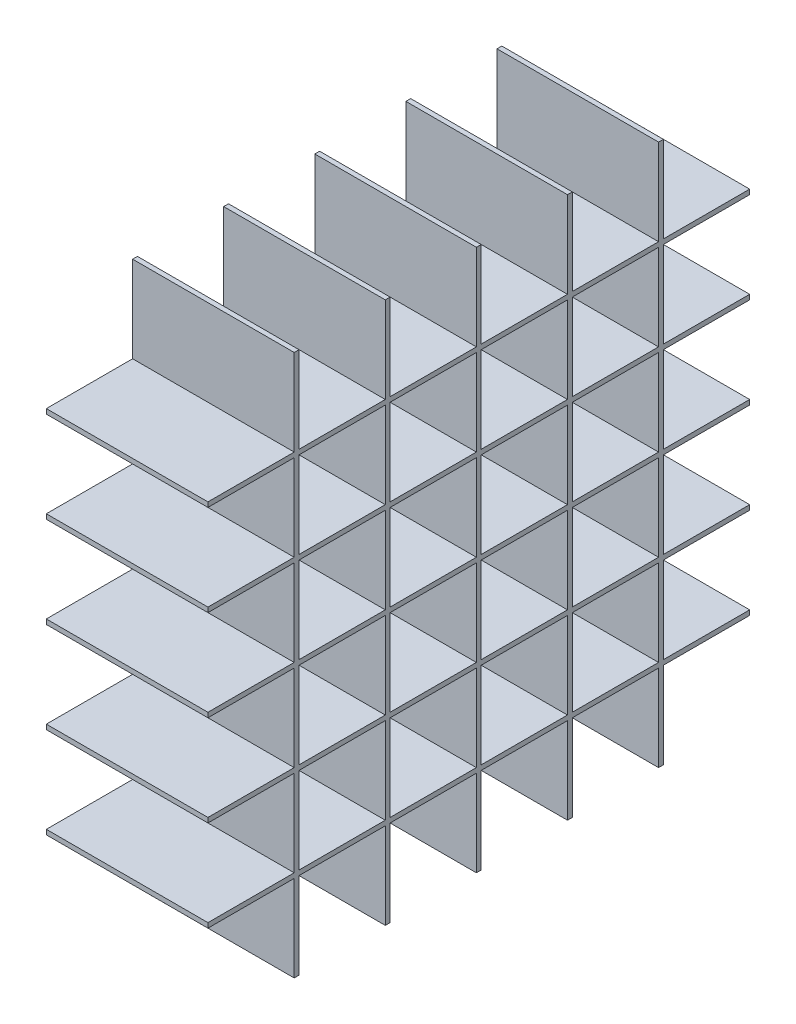
SolidWorks part; units mm, degrees
material "3003 Alloy"
ref_plane "Front Plane" through (0, 0, 0) normal (0, 0, 1) x (1, 0, 0)
ref_plane "Top Plane" through (0, 0, 0) normal (0, 1, 0) x (1, 0, 0)
ref_plane "Right Plane" through (0, 0, 0) normal (1, 0, 0) x (0, 0, -1)
sketch "Sketch1" plane through (0, 0, 0) normal (1, 0, 0) x (0, 0, -1)
  line L1 (-114.3, 114.3) -> (114.3, 114.3)
  line L2 (-114.3, 114.3) -> (-114.3, -114.3)
  line L3 (-114.3, -114.3) -> (114.3, -114.3)
  line L4 (114.3, 114.3) -> (114.3, -114.3)
  line L5 (-114.3, 114.3) -> (114.3, -114.3) construction
  line L6 (-114.3, -114.3) -> (114.3, 114.3) construction
  point P0 (0, 0)
  dimension "D1" = 228.6
  dimension "D2" = 228.6
extrude "Boss-Extrude1" add sketch "Sketch1" along normal blind 67
sketch "Sketch2" plane through (67, 0, 0) normal (1, 0, 0) x (0, 0, -1)
  line L0 (-114.3, 114.3) -> (-114.3, -114.3) construction
  line L1 (-112.3, 112.3) -> (-76.534, 112.3)
  line L2 (-112.3, 112.3) -> (-112.3, 76.534)
  line L3 (-112.3, 76.534) -> (-76.534, 76.534)
  line L4 (-76.534, 112.3) -> (-76.534, 76.534)
  line L5 (114.3, 114.3) -> (-114.3, 114.3) construction
  line L6 (-75.534, 112.3) -> (-75.534, 73.2554) construction
  line L7 (-74.534, 112.3) -> (-74.534, 76.534)
  line L8 (-38.768, 76.534) -> (-74.534, 76.534)
  line L9 (-38.768, 112.3) -> (-38.768, 76.534)
  line L10 (-38.768, 112.3) -> (-74.534, 112.3)
  line L11 (-37.768, 112.3) -> (-37.768, 75.534) construction
  line L12 (36.764, 76.534) -> (0.998, 76.534)
  line L13 (36.764, 112.3) -> (36.764, 76.534)
  line L14 (36.764, 112.3) -> (0.998, 112.3)
  line L15 (0.998, 112.3) -> (0.998, 76.534)
  line L16 (-36.768, 76.534) -> (-1.002, 76.534)
  line L17 (-1.002, 112.3) -> (-1.002, 76.534)
  line L18 (-36.768, 112.3) -> (-1.002, 112.3)
  line L19 (-36.768, 112.3) -> (-36.768, 76.534)
  line L20 (37.764, 112.3) -> (37.764, 70.4589) construction
  line L21 (38.764, 76.534) -> (74.53, 76.534)
  line L22 (112.296, 76.534) -> (76.53, 76.534)
  line L23 (112.296, 112.3) -> (112.296, 76.534)
  line L24 (74.53, 112.3) -> (74.53, 76.534)
  line L25 (76.53, 112.3) -> (76.53, 76.534)
  line L26 (112.296, 112.3) -> (76.53, 112.3)
  line L27 (38.764, 112.3) -> (74.53, 112.3)
  line L28 (38.764, 112.3) -> (38.764, 76.534)
  line L29 (-112.3, 75.534) -> (114.3, 75.534) construction
  line L30 (114.3, -114.3) -> (114.3, 114.3) construction
  line L31 (38.764, 74.534) -> (74.53, 74.534)
  line L32 (112.296, 74.534) -> (76.53, 74.534)
  line L33 (112.296, 38.768) -> (76.53, 38.768)
  line L34 (38.764, 38.768) -> (74.53, 38.768)
  line L35 (36.764, 74.534) -> (0.998, 74.534)
  line L36 (36.764, 38.768) -> (0.998, 38.768)
  line L37 (36.764, 38.768) -> (36.764, 74.534)
  line L38 (38.764, 38.768) -> (38.764, 74.534)
  line L39 (74.53, 38.768) -> (74.53, 74.534)
  line L40 (76.53, 38.768) -> (76.53, 74.534)
  line L41 (112.296, 38.768) -> (112.296, 74.534)
  line L42 (0.998, 38.768) -> (0.998, 74.534)
  line L43 (-1.002, 38.768) -> (-1.002, 74.534)
  line L44 (-36.768, 74.534) -> (-1.002, 74.534)
  line L45 (-36.768, 38.768) -> (-36.768, 74.534)
  line L46 (-36.768, 38.768) -> (-1.002, 38.768)
  line L47 (-38.768, 74.534) -> (-74.534, 74.534)
  line L48 (-38.768, 38.768) -> (-38.768, 74.534)
  line L49 (-38.768, 38.768) -> (-74.534, 38.768)
  line L50 (-74.534, 38.768) -> (-74.534, 74.534)
  line L51 (-76.534, 38.768) -> (-76.534, 74.534)
  line L52 (-112.3, 74.534) -> (-76.534, 74.534)
  line L53 (-112.3, 38.768) -> (-112.3, 74.534)
  line L54 (-112.3, 38.768) -> (-76.534, 38.768)
  line L55 (-112.3, 37.768) -> (112.296, 37.768) construction
  line L56 (-112.3, 36.768) -> (-112.3, 1.002)
  line L57 (-112.3, 1.002) -> (-76.534, 1.002)
  line L58 (-112.3, 36.768) -> (-76.534, 36.768)
  line L59 (-38.768, 36.768) -> (-74.534, 36.768)
  line L60 (-38.768, 1.002) -> (-74.534, 1.002)
  line L61 (-76.534, 36.768) -> (-76.534, 1.002)
  line L62 (-74.534, 36.768) -> (-74.534, 1.002)
  line L63 (-36.768, 1.002) -> (-1.002, 1.002)
  line L64 (-38.768, 36.768) -> (-38.768, 1.002)
  line L65 (-36.768, 36.768) -> (-36.768, 1.002)
  line L66 (-36.768, 36.768) -> (-1.002, 36.768)
  line L67 (-1.002, 36.768) -> (-1.002, 1.002)
  line L68 (0.998, 36.768) -> (0.998, 1.002)
  line L69 (36.764, 36.768) -> (0.998, 36.768)
  line L70 (36.764, 36.768) -> (36.764, 1.002)
  line L71 (36.764, 1.002) -> (0.998, 1.002)
  line L72 (38.764, 1.002) -> (74.53, 1.002)
  line L73 (38.764, 36.768) -> (38.764, 1.002)
  line L74 (38.764, 36.768) -> (74.53, 36.768)
  line L75 (74.53, 36.768) -> (74.53, 1.002)
  line L76 (76.53, 36.768) -> (76.53, 1.002)
  line L77 (112.296, 36.768) -> (76.53, 36.768)
  line L78 (112.296, 36.768) -> (112.296, 1.002)
  line L79 (112.296, 1.002) -> (76.53, 1.002)
  line L80 (112.296, -0.998) -> (76.53, -0.998)
  line L81 (112.296, -36.764) -> (112.296, -0.998)
  line L82 (112.296, -36.764) -> (76.53, -36.764)
  line L83 (76.53, -36.764) -> (76.53, -0.998)
  line L84 (74.53, -36.764) -> (74.53, -0.998)
  line L85 (38.764, -0.998) -> (74.53, -0.998)
  line L86 (38.764, -36.764) -> (38.764, -0.998)
  line L87 (38.764, -36.764) -> (74.53, -36.764)
  line L88 (36.764, -0.998) -> (0.998, -0.998)
  line L89 (36.764, -36.764) -> (36.764, -0.998)
  line L90 (36.764, -36.764) -> (0.998, -36.764)
  line L91 (0.998, -36.764) -> (0.998, -0.998)
  line L92 (-1.002, -36.764) -> (-1.002, -0.998)
  line L93 (-36.768, -0.998) -> (-1.002, -0.998)
  line L94 (-36.768, -36.764) -> (-36.768, -0.998)
  line L95 (-36.768, -36.764) -> (-1.002, -36.764)
  line L96 (-38.768, -36.764) -> (-38.768, -0.998)
  line L97 (-38.768, -0.998) -> (-74.534, -0.998)
  line L98 (-74.534, -36.764) -> (-74.534, -0.998)
  line L99 (-38.768, -36.764) -> (-74.534, -36.764)
  line L100 (-76.534, -36.764) -> (-76.534, -0.998)
  line L101 (-112.3, -0.998) -> (-76.534, -0.998)
  line L102 (-112.3, -36.764) -> (-112.3, -0.998)
  line L103 (-112.3, -36.764) -> (-76.534, -36.764)
  line L104 (-112.3, -37.764) -> (112.296, -37.764) construction
  line L105 (38.764, -38.764) -> (74.53, -38.764)
  line L106 (112.296, -38.764) -> (76.53, -38.764)
  line L107 (112.296, -38.764) -> (112.296, -74.53)
  line L108 (112.296, -112.296) -> (112.296, -76.53)
  line L109 (112.296, -112.296) -> (76.53, -112.296)
  line L110 (76.53, -112.296) -> (76.53, -76.53)
  line L111 (112.296, -76.53) -> (76.53, -76.53)
  line L112 (112.296, -74.53) -> (76.53, -74.53)
  line L113 (76.53, -38.764) -> (76.53, -74.53)
  line L114 (74.53, -38.764) -> (74.53, -74.53)
  line L115 (74.53, -112.296) -> (74.53, -76.53)
  line L116 (38.764, -112.296) -> (74.53, -112.296)
  line L117 (38.764, -76.53) -> (74.53, -76.53)
  line L118 (38.764, -74.53) -> (74.53, -74.53)
  line L119 (38.764, -38.764) -> (38.764, -74.53)
  line L120 (38.764, -112.296) -> (38.764, -76.53)
  line L121 (36.764, -112.296) -> (36.764, -76.53)
  line L122 (36.764, -112.296) -> (0.998, -112.296)
  line L123 (36.764, -76.53) -> (0.998, -76.53)
  line L124 (36.764, -74.53) -> (0.998, -74.53)
  line L125 (36.764, -38.764) -> (36.764, -74.53)
  line L126 (36.764, -38.764) -> (0.998, -38.764)
  line L127 (-1.002, -38.764) -> (-1.002, -74.53)
  line L128 (0.998, -38.764) -> (0.998, -74.53)
  line L129 (0.998, -112.296) -> (0.998, -76.53)
  line L130 (-1.002, -112.296) -> (-1.002, -76.53)
  line L131 (-36.768, -76.53) -> (-1.002, -76.53)
  line L132 (-36.768, -74.53) -> (-1.002, -74.53)
  line L133 (-36.768, -38.764) -> (-1.002, -38.764)
  line L134 (-36.768, -112.296) -> (-1.002, -112.296)
  line L135 (-38.768, -112.296) -> (-38.768, -76.53)
  line L136 (-36.768, -112.296) -> (-36.768, -76.53)
  line L137 (-36.768, -38.764) -> (-36.768, -74.53)
  line L138 (-38.768, -38.764) -> (-38.768, -74.53)
  line L139 (-38.768, -38.764) -> (-74.534, -38.764)
  line L140 (-74.534, -38.764) -> (-74.534, -74.53)
  line L141 (-38.768, -74.53) -> (-74.534, -74.53)
  line L142 (-38.768, -76.53) -> (-74.534, -76.53)
  line L143 (-74.534, -112.296) -> (-74.534, -76.53)
  line L144 (-38.768, -112.296) -> (-74.534, -112.296)
  line L145 (-112.3, -112.296) -> (-76.534, -112.296)
  line L146 (-112.3, -74.53) -> (-76.534, -74.53)
  line L147 (-112.3, -38.764) -> (-112.3, -74.53)
  line L148 (-112.3, -38.764) -> (-76.534, -38.764)
  line L149 (-112.3, -112.296) -> (-112.3, -76.53)
  line L150 (-112.3, -76.53) -> (-76.534, -76.53)
  line L151 (-76.534, -112.296) -> (-76.534, -76.53)
  line L152 (-76.534, -38.764) -> (-76.534, -74.53)
  point P114 (-56.651, -36.764)
  dimension "D1" = 2
  dimension "D2" = 2
  dimension "D3" = 35.766
  dimension "D4" = 35.766
  dimension "D5" = 1
  dimension "D6" = 1
  dimension "D7" = 1
  dimension "D8" = 1
  dimension "D9" = 1
  dimension "D10" = 1
extrude "Cut-Extrude1" cut sketch "Sketch2" against normal blind 76.2
sketch "Sketch4" plane through (0, -114.3, 0) normal (0, 1, 0) x (1, 0, 0)
  line L0 (67, -112.3) -> (0, -112.3)
  line L1 (67, -76.534) -> (0, -76.534)
  line L2 (67, -74.534) -> (0, -74.534)
  line L3 (67, -38.768) -> (0, -38.768)
  line L4 (67, -36.768) -> (0, -36.768)
  line L5 (67, -1.002) -> (0, -1.002)
  line L6 (67, 0.998) -> (0, 0.998)
  line L7 (67, 36.764) -> (0, 36.764)
  line L8 (67, 38.764) -> (0, 38.764)
  line L9 (67, 74.53) -> (0, 74.53)
  line L10 (67, 76.53) -> (0, 76.53)
  line L11 (67, 112.296) -> (0, 112.296)
  line L12 (0, 112.296) -> (0, 76.53)
  line L13 (67, 112.296) -> (67, 76.53)
  line L14 (0, 74.53) -> (0, 38.764)
  line L15 (67, 74.53) -> (67, 38.764)
  line L16 (0, 36.764) -> (0, 0.998)
  line L17 (67, 36.764) -> (67, 0.998)
  line L18 (67, -1.002) -> (67, -36.768)
  line L19 (0, -1.002) -> (0, -36.768)
  line L21 (0, -38.768) -> (0, -74.534)
  line L22 (67, -38.768) -> (67, -74.534)
  line L23 (67, -76.534) -> (67, -112.3)
  line L24 (0, -76.534) -> (0, -112.3)
extrude "Cut-Extrude3" cut sketch "Sketch4" against normal blind 4 and the other way blind 4
sketch "Sketch5" plane through (0, 0, 114.3) normal (0, 0, 1) x (1, 0, 0)
  line L0 (0, -76.53) -> (67, -76.53)
  line L1 (0, -74.53) -> (67, -74.53)
  line L2 (0, -38.764) -> (67, -38.764)
  line L3 (0, -36.764) -> (67, -36.764)
  line L4 (0, -0.998) -> (67, -0.998)
  line L5 (0, 1.002) -> (67, 1.002)
  line L6 (0, 36.768) -> (67, 36.768)
  line L7 (0, 38.768) -> (67, 38.768)
  line L8 (0, 74.534) -> (67, 74.534)
  line L9 (0, 76.534) -> (67, 76.534)
  line L10 (0, 112.3) -> (67, 112.3)
  line L11 (0, -114.3) -> (0, -76.53)
  line L12 (67, -114.3) -> (67, -76.53)
  line L13 (0, -74.53) -> (0, -38.764)
  line L14 (67, -74.53) -> (67, -38.764)
  line L15 (0, -36.764) -> (0, -0.998)
  line L16 (67, -36.764) -> (67, -0.998)
  line L17 (67, 1.002) -> (67, 36.768)
  line L18 (0, 1.002) -> (0, 36.768)
  line L19 (0, 38.768) -> (0, 74.534)
  line L20 (67, 38.768) -> (67, 74.534)
  line L21 (67, 76.534) -> (67, 112.3)
  line L22 (0, 76.534) -> (0, 112.3)
  line M1 (0, 114.3) -> (0, -114.3)
  line M2 (0, -114.3) -> (67, -114.3)
  line M3 (67, -114.3) -> (67, 114.3)
extrude "Cut-Extrude4" cut sketch "Sketch5" against normal blind 4 and the other way blind 4 contours L0 M1 M2 M3 | L2 L1 M1 M3 | L4 L3 M1 M3 | L6 L5 M1 M3 | L8 L7 M1 M3 | L10 L9 M1 M3 region at (33.5, -95.415, 114.3) region at (33.5, -56.647, 114.3) region at (33.5, -18.881, 114.3) region at (33.5, 18.885, 114.3) region at (33.5, 56.651, 114.3) region at (33.5, 94.417, 114.3)
sketch "Sketch6" plane through (0, 0, -114.3) normal (0, 0, 1) x (1, 0, 0)
  line L0 (0, 112.3) -> (67, 112.3)
  line L1 (0, 76.534) -> (67, 76.534)
  line L2 (0, 74.534) -> (67, 74.534)
  line L3 (0, 38.768) -> (67, 38.768)
  line L4 (0, 36.768) -> (67, 36.768)
  line L5 (0, -0.998) -> (67, -0.998)
  line L6 (0, 1.002) -> (67, 1.002)
  line L7 (0, -76.53) -> (67, -76.53)
  line L8 (0, -74.53) -> (67, -74.53)
  line L9 (0, -36.764) -> (67, -36.764)
  line L10 (0, -38.764) -> (67, -38.764)
  line L11 (0, 112.3) -> (0, 76.534)
  line L12 (0, 74.534) -> (0, 38.768)
  line L13 (0, 36.768) -> (0, 1.002)
  line L14 (0, -0.998) -> (0, -36.764)
  line L15 (0, -38.764) -> (0, -74.53)
  line L16 (0, -76.53) -> (0, -114.3)
  line L17 (67, 112.3) -> (67, 76.534)
  line L18 (67, 74.534) -> (67, 38.768)
  line L19 (67, 36.768) -> (67, 1.002)
  line L20 (67, -0.998) -> (67, -36.764)
  line L21 (67, -38.764) -> (67, -74.53)
  line L22 (67, -76.53) -> (67, -114.3)
  line M1 (0, -114.3) -> (0, 114.3)
  line M3 (67, 114.3) -> (67, -114.3)
  line M4 (67, -114.3) -> (0, -114.3)
extrude "Cut-Extrude5" cut sketch "Sketch6" against normal blind 4 and the other way blind 4 contours L1 L0 M1 M3 | L3 L2 M1 M3 | L6 L4 M1 M3 | L9 L5 M1 M3 | L10 L8 M1 M3 | L7 M1 M3 M4 region at (33.5, 94.417, -114.3) region at (33.5, 56.651, -114.3) region at (33.5, 18.885, -114.3) region at (33.5, -18.881, -114.3) region at (33.5, -56.647, -114.3) region at (33.5, -95.415, -114.3)
sketch "Sketch9" plane through (0, 114.3, 0) normal (0, 1, 0) x (1, 0, 0)
  line L0 (0, -76.534) -> (67, -76.534)
  line L1 (0, -74.534) -> (67, -74.534)
  line L2 (0, -38.768) -> (67, -38.768)
  line L3 (0, -36.768) -> (67, -36.768)
  line L4 (0, -1.002) -> (67, -1.002)
  line L5 (0, 0.998) -> (67, 0.998)
  line L6 (0, 36.764) -> (67, 36.764)
  line L7 (0, 38.764) -> (67, 38.764)
  line L8 (0, 74.53) -> (67, 74.53)
  line L9 (0, 76.53) -> (67, 76.53)
  line L10 (0, -114.3) -> (0, -76.534)
  line L11 (0, -74.534) -> (0, -38.768)
  line L12 (0, -36.768) -> (0, -1.002)
  line L13 (0, 0.998) -> (0, 36.764)
  line L14 (0, 38.764) -> (0, 74.53)
  line L15 (0, 76.53) -> (0, 114.3)
  line L16 (67, -114.3) -> (67, -76.534)
  line L17 (67, -74.534) -> (67, -38.768)
  line L18 (67, -36.768) -> (67, -1.002)
  line L19 (67, 0.998) -> (67, 36.764)
  line L20 (67, 38.764) -> (67, 74.53)
  line L21 (67, 76.53) -> (67, 114.3)
  line M1 (0, 114.3) -> (0, -114.3)
  line M2 (0, -114.3) -> (67, -114.3)
  line M3 (67, -114.3) -> (67, 114.3)
  line M4 (67, 114.3) -> (0, 114.3)
extrude "Cut-Extrude6" cut sketch "Sketch9" against normal blind 4 and the other way blind 4 contours L0 M1 M2 M3 | L2 L1 M1 M3 | L4 L3 M1 M3 | L6 L5 M1 M3 | L8 L7 M1 M3 | L9 M1 M3 M4 region at (33.5, 114.3, 95.417) region at (33.5, 114.3, 56.651) region at (33.5, 114.3, 18.885) region at (33.5, 114.3, -18.881) region at (33.5, 114.3, -56.647) region at (33.5, 114.3, -95.415)
sketch "Sketch10" plane through (0, 0, 76.534) normal (0, 0, 1) x (1, 0, 0)
  line L0 (0, -114.3) -> (67, -114.3)
  line L1 (67, -114.3) -> (67, -112.3)
  line L2 (67, -114.3) -> (67, -76.53) construction
  line L3 (67, -112.3) -> (0, -112.3)
  line L4 (0, -114.3) -> (0, -76.53) construction
  line L5 (0, -112.3) -> (0, -114.3)
  line L6 (0, 114.3) -> (67, 114.3)
  line L7 (67, 114.3) -> (67, 112.3)
  line L8 (67, 76.534) -> (67, 114.3) construction
  line L9 (67, 112.3) -> (0, 112.3)
  line L10 (0, 76.534) -> (0, 114.3) construction
  line L11 (0, 112.3) -> (0, 114.3)
  dimension "D1" = 2
  dimension "D2" = 2
extrude "Cut-Extrude7" cut sketch "Sketch10" against normal through all
sketch "Sketch11" plane through (0, -76.53, 0) normal (0, -1, 0) x (-1, 0, 0)
  line L0 (-67, 114.3) -> (0, 114.3)
  line L1 (0, 114.3) -> (0, 112.3)
  line L2 (0, 114.3) -> (0, 76.53) construction
  line L3 (0, 112.3) -> (-67, 112.3)
  line L4 (-67, 114.3) -> (-67, 76.53) construction
  line L5 (-67, 112.3) -> (-67, 114.3)
  line L6 (-67, 114.3) -> (-76.1621, 114.1122)
  line L7 (-67, -114.3) -> (0, -114.3)
  line L8 (0, -114.3) -> (0, -112.3)
  line L9 (0, -76.534) -> (0, -114.3) construction
  line L10 (0, -112.3) -> (-67, -112.3)
  line L11 (-67, -76.534) -> (-67, -114.3) construction
  line L12 (-67, -112.3) -> (-67, -114.3)
  line M3 (-67, 114.3) -> (-67, 76.53)
  line M5 (0, 76.53) -> (0, 114.3)
  line M6 (0, 114.3) -> (-67, 114.3)
  dimension "D1" = 2
  dimension "D2" = 2
extrude "Cut-Extrude8" cut sketch "Sketch11" against normal through all contours L3 M5 M6 M3 | L10 L12 L7 L8 region at (33.5, -76.53, -113.3)
